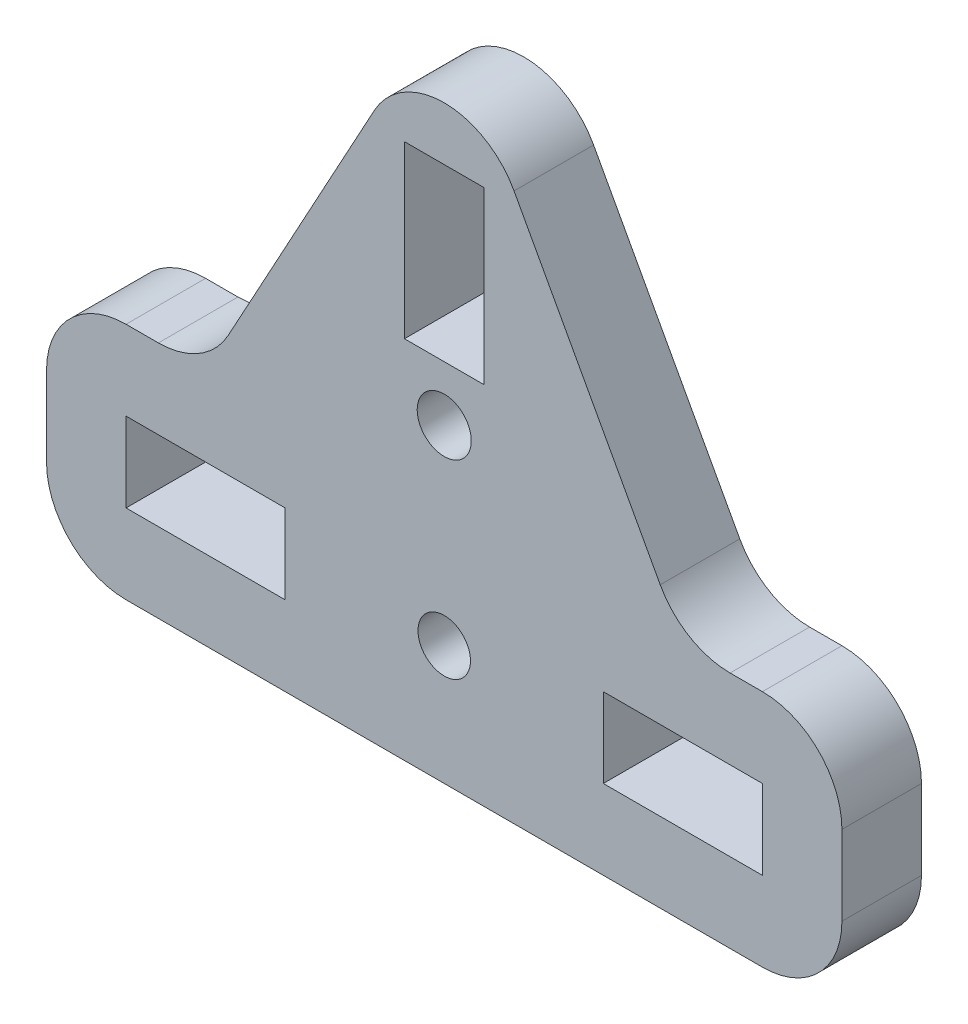
SolidWorks part; units mm, degrees
ref_plane "Front Plane" through (0, 0, 0) normal (0, 0, 1) x (1, 0, 0)
ref_plane "Top Plane" through (0, 0, 0) normal (0, 1, 0) x (1, 0, 0)
ref_plane "Right Plane" through (0, 0, 0) normal (1, 0, 0) x (0, 0, -1)
sketch "Sketch1" plane through (0, 0, 0) normal (0, 0, 1) x (1, 0, 0)
  line L1 (-31.75, -9.525) -> (31.75, -9.525)
  line L2 (-31.75, -9.525) -> (-31.75, 9.525)
  line L3 (-31.75, 9.525) -> (31.75, 9.525)
  line L4 (31.75, -9.525) -> (31.75, 9.525)
  line L5 (-31.75, -9.525) -> (31.75, 9.525) construction
  line L6 (-31.75, 9.525) -> (31.75, -9.525) construction
  point P0 (0, 0)
  dimension "D1" = 19.05
  dimension "D2" = 63.5
extrude "Boss-Extrude1" add sketch "Sketch1" along normal blind 6.35
sketch "Sketch2" plane through (0, 0, 6.35) normal (0, 0, 1) x (1, 0, 0)
  line L0 (0, 3.175) -> (0, -3.175) construction
  line L1 (-31.75, -9.525) -> (31.75, -9.525) construction
  line L2 (-31.75, -3.175) -> (31.75, -3.175) construction
  line L3 (-31.75, 9.525) -> (-31.75, -9.525) construction
  line L4 (31.75, -9.525) -> (31.75, 9.525) construction
  line L5 (-31.75, 3.175) -> (31.75, 3.175) construction
  line L7 (-25.4, 3.175) -> (-12.7, 3.175)
  line L8 (-25.4, 3.175) -> (-25.4, -3.175)
  line L9 (-25.4, -3.175) -> (-12.7, -3.175)
  line L10 (-12.7, 3.175) -> (-12.7, -3.175)
  line L11 (12.7, 3.175) -> (25.4, 3.175)
  line L12 (12.7, 3.175) -> (12.7, -3.175)
  line L13 (12.7, -3.175) -> (25.4, -3.175)
  line L14 (25.4, 3.175) -> (25.4, -3.175)
  circle A0 centre (0, 0) radius 2.0955
  dimension "D3" = 4.191
  dimension "D1" = 6.35
  dimension "D2" = 6.35
  dimension "D4" = 12.7
  dimension "D5" = 12.7
  dimension "D6" = 12.7
  dimension "D7" = 12.7
extrude "Cut-Extrude1" cut sketch "Sketch2" against normal blind 6.35
sketch "Sketch3" plane through (0, 0, 6.35) normal (0, 0, 1) x (1, 0, 0)
  line L0 (0, 0) -> (0, 44.45) construction
  line L1 (0, 9.525) -> (-19.05, 9.525)
  line L2 (31.75, 9.525) -> (-31.75, 9.525) construction
  line L3 (-19.05, 9.525) -> (0, 44.45)
  line L4 (0, 44.45) -> (19.05, 9.525)
  line L5 (0, 44.45) -> (0, 9.525)
  line L6 (19.05, 9.525) -> (0, 9.525)
  circle A0 centre (0, 31.1891) radius 6.35
  line M11 (31.75, 9.525) -> (-31.75, 9.525)
  dimension "D3" = 12.7
  dimension "D1" = 34.925
  dimension "D2" = 19.05
extrude "Boss-Extrude2" add sketch "Sketch3" against normal blind 6.35 contours A0 L3 L5 M11 | L5 A0 | A0 L5 | A0 L5 L4 M11 region at (-7.5503, 17.565, 6.35) region at (7.5503, 17.565, 6.35) region at (-2.695, 31.1891, 6.35) region at (2.695, 31.1891, 6.35)
sketch "Sketch4" plane through (0, 0, 0) normal (0, 0, -1) x (-1, 0, 0)
  line L4 (-3.175, 19.6364) -> (3.175, 19.6364)
  line L5 (3.175, 19.6364) -> (3.175, 33.2635)
  line L6 (3.175, 33.2635) -> (-3.175, 33.2635)
  line L7 (-3.175, 33.2635) -> (-3.175, 19.6364)
  line L8 (-3.175, 19.6364) -> (3.175, 19.6364)
  line L9 (3.175, 19.6364) -> (3.175, 33.2635)
  line L10 (3.175, 33.2635) -> (-3.175, 33.2635)
  line L11 (-3.175, 33.2635) -> (-3.175, 19.6364)
  circle A0 centre (0, 15.24) radius 2.159 construction
  circle A1 centre (0, 15.24) radius 2.159
  dimension "D1" = 0
extrude "Cut-Extrude3" cut sketch "Sketch4" against normal blind 6.35
fillet "Fillet1" radius 6.35 6 edges at (31.75, -9.525, 3.175) (31.75, 9.525, 3.175) (-31.75, -9.525, 3.175) (-31.75, 9.525, 3.175)
